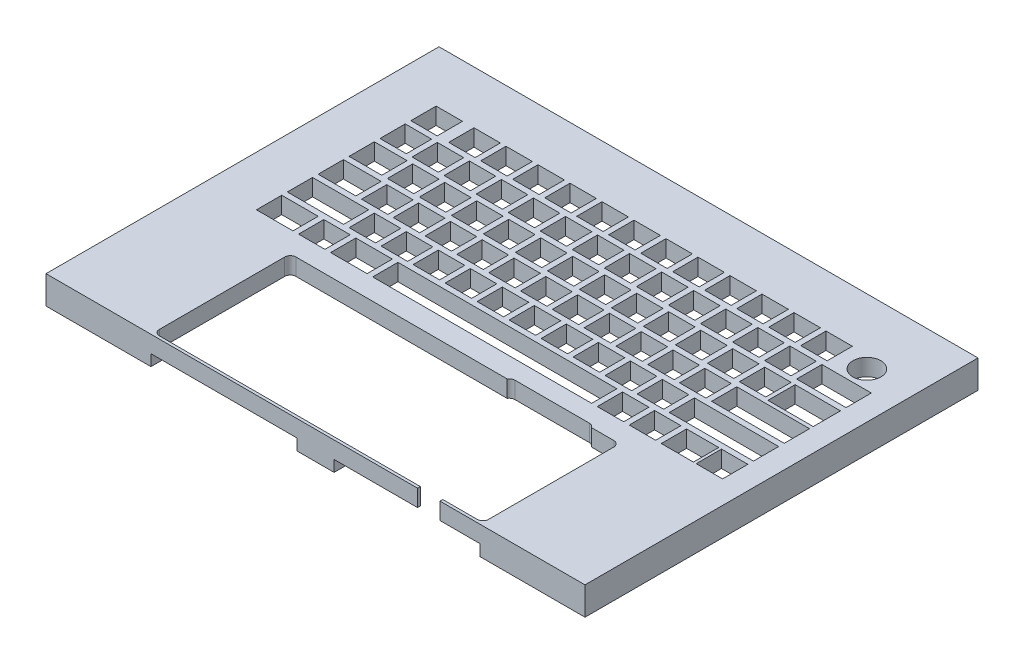
SolidWorks part; units mm, degrees
ref_plane "Front Plane" through (0, 0, 0) normal (0, 0, 1) x (1, 0, 0)
ref_plane "Top Plane" through (0, 0, 0) normal (0, 1, 0) x (1, 0, 0)
ref_plane "Right Plane" through (0, 0, 0) normal (1, 0, 0) x (0, 0, -1)
sketch "Sketch1" plane through (0, 0, 0) normal (0, 1, 0) x (1, 0, 0)
  line L0 (5.08, 5.08) -> (238.76, 5.08)
  line L1 (0, 0) -> (243.84, 0)
  line L2 (0, 0) -> (0, 177.8)
  line L3 (0, 177.8) -> (243.84, 177.8)
  line L4 (243.84, 0) -> (243.84, 177.8)
  line L5 (238.76, 5.08) -> (238.76, 172.72)
  line L6 (5.08, 172.72) -> (238.76, 172.72)
  line L7 (5.08, 5.08) -> (5.08, 172.72)
  dimension "D1" = 177.8
  dimension "D2" = 243.84
  dimension "D3" = 5.08
extrude "Boss-Extrude7" add sketch "Sketch1" along normal blind 12.7
sketch "Sketch6" plane through (0, 12.7, 0) normal (0, 1, 0) x (1, 0, 0)
  line L0 (5.08, 172.72) -> (5.08, 5.08)
  line L1 (5.08, 5.08) -> (238.76, 5.08)
  line L2 (238.76, 5.08) -> (238.76, 172.72)
  line L3 (238.76, 172.72) -> (5.08, 172.72)
extrude "Boss-Extrude8" add sketch "Sketch6" against normal blind 7.62
sketch "Sketch7" plane through (0, 12.7, 0) normal (0, 1, 0) x (1, 0, 0)
  line L0 (0, 0) -> (243.84, 0) construction
  line L1 (0, 177.8) -> (0, 0) construction
  line L2 (243.84, 0) -> (243.84, 177.8) construction
  line L3 (196.37, 1.27) -> (178.2581, 1.27)
  line L4 (47.47, 1.27) -> (47.47, 63.07)
  line L6 (196.37, 63.07) -> (196.37, 1.27)
  line L8 (47.47, 32.17) -> (0, 32.17) construction
  line L9 (196.37, 32.17) -> (243.84, 32.17) construction
  line L11 (168.0981, 0) -> (178.2581, 0)
  line L12 (178.2581, 0) -> (178.2581, 1.27)
  line L14 (157.9954, 1.27) -> (47.47, 1.27)
  line L15 (157.9954, 1.27) -> (168.0981, 1.27)
  line L16 (168.0981, 1.27) -> (168.0981, 0)
  line L18 (183.67, 64.34) -> (145.57, 64.34)
  line L20 (196.37, 63.07) -> (183.67, 63.07)
  line L21 (145.57, 63.07) -> (47.47, 63.07)
  line L22 (183.67, 63.07) -> (183.67, 64.34)
  line L23 (145.57, 63.07) -> (145.57, 64.34)
  dimension "D1" = 1.27
  dimension "D2" = 148.9
  dimension "D3" = 61.8
  dimension "D4" = 10.16
  dimension "D5" = 38.1
  dimension "D6" = 12.7
  dimension "D7" = 1.27
extrude "Cut-Extrude2" cut sketch "Sketch7" against normal blind 8 contours L4 L21 L23 L18 L22 L20 L6 L3 L12 L11 L16 L15 L14
fillet "Fillet1" radius 2.54 4 edges at (47.47, 8.89, -63.07) (47.47, 8.7, -1.27) (196.37, 8.7, -1.27) (196.37, 8.89, -63.07)
fillet "Fillet2" radius 2.54 2 edges at (145.57, 8.89, -64.34) (183.67, 8.89, -64.34)
sketch "Sketch8" plane through (0, 12.7, 0) normal (0, 1, 0) x (1, 0, 0)
  line L0 (50.5293, 86.591) -> (50.5293, 97.9956)
  line L1 (50.5293, 97.9956) -> (62.5181, 97.9956)
  line L2 (62.5181, 97.9956) -> (62.5181, 86.591)
  line L3 (62.5181, 86.591) -> (50.5293, 86.591)
  line L4 (76.9961, 86.591) -> (65.0073, 86.591)
  line L5 (65.0073, 86.591) -> (65.0073, 97.9956)
  line L6 (65.0073, 97.9956) -> (76.9961, 97.9956)
  line L7 (76.9961, 97.9956) -> (76.9961, 86.591)
  line L8 (91.4741, 86.591) -> (79.4853, 86.591)
  line L9 (79.4853, 86.591) -> (79.4853, 97.9956)
  line L10 (79.4853, 97.9956) -> (91.4741, 97.9956)
  line L11 (91.4741, 97.9956) -> (91.4741, 86.591)
  line L12 (105.9521, 86.591) -> (93.9633, 86.591)
  line L13 (93.9633, 86.591) -> (93.9633, 97.9956)
  line L14 (93.9633, 97.9956) -> (105.9521, 97.9956)
  line L15 (105.9521, 97.9956) -> (105.9521, 86.591)
  line L16 (120.4301, 86.591) -> (108.4413, 86.591)
  line L17 (108.4413, 86.591) -> (108.4413, 97.9956)
  line L18 (108.4413, 97.9956) -> (120.4301, 97.9956)
  line L19 (120.4301, 97.9956) -> (120.4301, 86.591)
  line L20 (134.9081, 86.591) -> (122.9193, 86.591)
  line L21 (122.9193, 86.591) -> (122.9193, 97.9956)
  line L22 (122.9193, 97.9956) -> (134.9081, 97.9956)
  line L23 (134.9081, 97.9956) -> (134.9081, 86.591)
  line L24 (149.3861, 86.591) -> (137.3973, 86.591)
  line L25 (137.3973, 86.591) -> (137.3973, 97.9956)
  line L26 (137.3973, 97.9956) -> (149.3861, 97.9956)
  line L27 (149.3861, 97.9956) -> (149.3861, 86.591)
  line L28 (163.8641, 86.591) -> (151.8753, 86.591)
  line L29 (151.8753, 86.591) -> (151.8753, 97.9956)
  line L30 (151.8753, 97.9956) -> (163.8641, 97.9956)
  line L31 (163.8641, 97.9956) -> (163.8641, 86.591)
  line L32 (178.3421, 86.591) -> (166.3533, 86.591)
  line L33 (166.3533, 86.591) -> (166.3533, 97.9956)
  line L34 (166.3533, 97.9956) -> (178.3421, 97.9956)
  line L35 (178.3421, 97.9956) -> (178.3421, 86.591)
  line L36 (192.8201, 86.591) -> (180.8313, 86.591)
  line L37 (180.8313, 86.591) -> (180.8313, 97.9956)
  line L38 (180.8313, 97.9956) -> (192.8201, 97.9956)
  line L39 (192.8201, 97.9956) -> (192.8201, 86.591)
  line L40 (120.4301, 92.2933) -> (122.9193, 92.2933) construction
  line L43 (120.4301, 92.2933) -> (0, 92.2933) construction
  line L44 (0, 177.8) -> (0, 0) construction
  line L45 (47.9893, 86.591) -> (22.5893, 86.591)
  line L46 (22.5893, 86.591) -> (22.5893, 97.9956)
  line L47 (22.5893, 97.9956) -> (47.9893, 97.9956)
  line L48 (47.9893, 97.9956) -> (47.9893, 86.591)
  line L55 (195.3601, 97.9956) -> (195.3601, 86.591)
  line L56 (195.3601, 86.591) -> (233.4601, 86.591)
  line L57 (233.4601, 86.591) -> (233.4601, 97.9956)
  line L58 (233.4601, 97.9956) -> (195.3601, 97.9956)
  line L59 (192.8201, 86.591) -> (195.3601, 86.591) construction
  line L60 (192.8201, 97.9956) -> (195.3601, 97.9956) construction
  line L61 (75.1673, 72.621) -> (75.1673, 84.051)
  line L62 (75.1673, 84.051) -> (174.2273, 84.051)
  line L63 (174.2273, 84.051) -> (174.2273, 72.621)
  line L64 (174.2273, 72.621) -> (75.1673, 72.621)
  line L65 (72.6273, 72.6364) -> (72.6273, 84.051)
  line L66 (72.6273, 84.051) -> (56.1173, 84.051)
  line L67 (56.1173, 84.051) -> (56.1173, 72.6364)
  line L68 (56.1173, 72.6364) -> (72.6273, 72.6364)
  line L69 (53.5773, 72.621) -> (53.5773, 84.051)
  line L70 (53.5773, 84.051) -> (41.6393, 84.051)
  line L71 (41.6393, 84.051) -> (41.6393, 72.621)
  line L72 (41.6393, 72.621) -> (53.5773, 72.621)
  line L73 (39.0993, 72.621) -> (39.0993, 84.051)
  line L74 (39.0993, 84.051) -> (22.5893, 84.051)
  line L75 (22.5893, 84.051) -> (22.5893, 72.621)
  line L76 (22.5893, 72.621) -> (39.0993, 72.621)
  line L78 (188.7052, 72.6364) -> (188.7052, 84.0664)
  line L79 (188.7052, 84.0664) -> (176.7672, 84.0664)
  line L80 (176.7672, 84.0664) -> (176.7672, 72.6364)
  line L81 (176.7672, 72.6364) -> (188.7052, 72.6364)
  line L96 (42.1943, 111.9656) -> (42.1943, 100.5356)
  line L97 (42.1943, 100.5356) -> (54.1323, 100.5356)
  line L98 (54.1323, 100.5356) -> (54.1323, 111.9656)
  line L99 (54.1323, 111.9656) -> (42.1943, 111.9656)
  line L100 (68.5217, 111.9656) -> (56.5837, 111.9656)
  line L101 (56.5837, 111.9656) -> (56.5837, 100.5356)
  line L102 (56.5837, 100.5356) -> (68.5217, 100.5356)
  line L103 (68.5217, 100.5356) -> (68.5217, 111.9656)
  line L104 (82.911, 111.9656) -> (70.973, 111.9656)
  line L105 (70.973, 111.9656) -> (70.973, 100.5356)
  line L106 (70.973, 100.5356) -> (82.911, 100.5356)
  line L107 (82.911, 100.5356) -> (82.911, 111.9656)
  line L108 (97.3003, 111.9656) -> (85.3623, 111.9656)
  line L109 (85.3623, 111.9656) -> (85.3623, 100.5356)
  line L110 (85.3623, 100.5356) -> (97.3003, 100.5356)
  line L111 (97.3003, 100.5356) -> (97.3003, 111.9656)
  line L112 (111.6896, 111.9656) -> (99.7516, 111.9656)
  line L113 (99.7516, 111.9656) -> (99.7516, 100.5356)
  line L114 (99.7516, 100.5356) -> (111.6896, 100.5356)
  line L115 (111.6896, 100.5356) -> (111.6896, 111.9656)
  line L116 (126.079, 111.9656) -> (114.141, 111.9656)
  line L117 (114.141, 111.9656) -> (114.141, 100.5356)
  line L118 (114.141, 100.5356) -> (126.079, 100.5356)
  line L119 (126.079, 100.5356) -> (126.079, 111.9656)
  line L120 (140.4683, 111.9656) -> (128.5303, 111.9656)
  line L121 (128.5303, 111.9656) -> (128.5303, 100.5356)
  line L122 (128.5303, 100.5356) -> (140.4683, 100.5356)
  line L123 (140.4683, 100.5356) -> (140.4683, 111.9656)
  line L124 (154.8576, 111.9656) -> (142.9196, 111.9656)
  line L125 (142.9196, 111.9656) -> (142.9196, 100.5356)
  line L126 (142.9196, 100.5356) -> (154.8576, 100.5356)
  line L127 (154.8576, 100.5356) -> (154.8576, 111.9656)
  line L128 (169.247, 111.9656) -> (157.309, 111.9656)
  line L129 (157.309, 111.9656) -> (157.309, 100.5356)
  line L130 (157.309, 100.5356) -> (169.247, 100.5356)
  line L131 (169.247, 100.5356) -> (169.247, 111.9656)
  line L132 (183.6363, 111.9656) -> (171.6983, 111.9656)
  line L133 (171.6983, 111.9656) -> (171.6983, 100.5356)
  line L134 (171.6983, 100.5356) -> (183.6363, 100.5356)
  line L135 (183.6363, 100.5356) -> (183.6363, 111.9656)
  line L136 (198.0256, 111.9656) -> (186.0876, 111.9656)
  line L137 (186.0876, 111.9656) -> (186.0876, 100.5356)
  line L138 (186.0876, 100.5356) -> (198.0256, 100.5356)
  line L139 (198.0256, 100.5356) -> (198.0256, 111.9656)
  line L140 (39.6543, 100.5356) -> (22.5893, 100.5356)
  line L141 (22.5893, 100.5356) -> (22.5893, 111.9656)
  line L142 (22.5893, 111.9656) -> (39.6543, 111.9656)
  line L143 (39.6543, 111.9656) -> (39.6543, 100.5356)
  line L144 (200.5656, 111.9656) -> (200.5656, 100.5356)
  line L145 (200.5656, 100.5356) -> (233.4601, 100.5356)
  line L146 (233.4601, 100.5356) -> (233.4601, 111.9656)
  line L147 (233.4601, 111.9656) -> (200.5656, 111.9656)
  line L156 (51.8757, 125.9592) -> (39.9377, 125.9592)
  line L157 (39.9377, 125.9592) -> (39.9377, 114.5056)
  line L158 (39.9377, 114.5056) -> (51.8757, 114.5056)
  line L159 (51.8757, 114.5056) -> (51.8757, 125.9592)
  line L196 (66.3537, 125.9592) -> (54.4157, 125.9592)
  line L197 (54.4157, 125.9592) -> (54.4157, 114.5056)
  line L198 (54.4157, 114.5056) -> (66.3537, 114.5056)
  line L199 (66.3537, 114.5056) -> (66.3537, 125.9592)
  line L200 (80.8317, 125.9592) -> (68.8937, 125.9592)
  line L201 (68.8937, 125.9592) -> (68.8937, 114.5056)
  line L202 (68.8937, 114.5056) -> (80.8317, 114.5056)
  line L203 (80.8317, 114.5056) -> (80.8317, 125.9592)
  line L204 (95.3097, 125.9592) -> (83.3717, 125.9592)
  line L205 (83.3717, 125.9592) -> (83.3717, 114.5056)
  line L206 (83.3717, 114.5056) -> (95.3097, 114.5056)
  line L207 (95.3097, 114.5056) -> (95.3097, 125.9592)
  line L208 (109.7877, 125.9592) -> (97.8497, 125.9592)
  line L209 (97.8497, 125.9592) -> (97.8497, 114.5056)
  line L210 (97.8497, 114.5056) -> (109.7877, 114.5056)
  line L211 (109.7877, 114.5056) -> (109.7877, 125.9592)
  line L212 (124.2657, 125.9592) -> (112.3277, 125.9592)
  line L213 (112.3277, 125.9592) -> (112.3277, 114.5056)
  line L214 (112.3277, 114.5056) -> (124.2657, 114.5056)
  line L215 (124.2657, 114.5056) -> (124.2657, 125.9592)
  line L216 (138.7437, 125.9592) -> (126.8057, 125.9592)
  line L217 (126.8057, 125.9592) -> (126.8057, 114.5056)
  line L218 (126.8057, 114.5056) -> (138.7437, 114.5056)
  line L219 (138.7437, 114.5056) -> (138.7437, 125.9592)
  line L220 (153.2217, 125.9592) -> (141.2837, 125.9592)
  line L221 (141.2837, 125.9592) -> (141.2837, 114.5056)
  line L222 (141.2837, 114.5056) -> (153.2217, 114.5056)
  line L223 (153.2217, 114.5056) -> (153.2217, 125.9592)
  line L224 (167.6997, 125.9592) -> (155.7617, 125.9592)
  line L225 (155.7617, 125.9592) -> (155.7617, 114.5056)
  line L226 (155.7617, 114.5056) -> (167.6997, 114.5056)
  line L227 (167.6997, 114.5056) -> (167.6997, 125.9592)
  line L228 (182.1777, 125.9592) -> (170.2397, 125.9592)
  line L229 (170.2397, 125.9592) -> (170.2397, 114.5056)
  line L230 (170.2397, 114.5056) -> (182.1777, 114.5056)
  line L231 (182.1777, 114.5056) -> (182.1777, 125.9592)
  line L232 (196.6557, 125.9592) -> (184.7177, 125.9592)
  line L233 (184.7177, 125.9592) -> (184.7177, 114.5056)
  line L234 (184.7177, 114.5056) -> (196.6557, 114.5056)
  line L235 (196.6557, 114.5056) -> (196.6557, 125.9592)
  line L236 (211.1337, 125.9592) -> (199.1957, 125.9592)
  line L237 (199.1957, 125.9592) -> (199.1957, 114.5056)
  line L238 (199.1957, 114.5056) -> (211.1337, 114.5056)
  line L239 (211.1337, 114.5056) -> (211.1337, 125.9592)
  line L240 (37.3977, 114.5056) -> (22.5893, 114.5056)
  line L241 (22.5893, 114.5056) -> (22.5893, 125.9592)
  line L242 (22.5893, 125.9592) -> (37.3977, 125.9592)
  line L243 (37.3977, 125.9592) -> (37.3977, 114.5056)
  line L244 (212.9454, 113.6508) -> (212.9454, 125.9592)
  line L245 (212.9454, 125.9592) -> (233.4601, 125.9592)
  line L246 (233.4601, 125.9592) -> (233.4601, 113.6508)
  line L247 (233.4601, 113.6508) -> (212.9454, 113.6508)
  line L248 (22.5893, 128.4992) -> (22.5893, 139.9292)
  line L249 (22.5893, 139.9292) -> (34.5273, 139.9292)
  line L250 (34.5273, 139.9292) -> (34.5273, 128.4992)
  line L251 (34.5273, 128.4992) -> (22.5893, 128.4992)
  line L252 (49.0288, 128.4992) -> (37.0908, 128.4992)
  line L253 (37.0908, 128.4992) -> (37.0908, 139.9292)
  line L254 (37.0908, 139.9292) -> (49.0288, 139.9292)
  line L255 (49.0288, 139.9292) -> (49.0288, 128.4992)
  line L256 (63.5303, 128.4992) -> (51.5923, 128.4992)
  line L257 (51.5923, 128.4992) -> (51.5923, 139.9292)
  line L258 (51.5923, 139.9292) -> (63.5303, 139.9292)
  line L259 (63.5303, 139.9292) -> (63.5303, 128.4992)
  line L260 (78.0318, 128.4992) -> (66.0938, 128.4992)
  line L261 (66.0938, 128.4992) -> (66.0938, 139.9292)
  line L262 (66.0938, 139.9292) -> (78.0318, 139.9292)
  line L263 (78.0318, 139.9292) -> (78.0318, 128.4992)
  line L264 (92.5334, 128.4992) -> (80.5954, 128.4992)
  line L265 (80.5954, 128.4992) -> (80.5954, 139.9292)
  line L266 (80.5954, 139.9292) -> (92.5334, 139.9292)
  line L267 (92.5334, 139.9292) -> (92.5334, 128.4992)
  line L268 (107.0349, 128.4992) -> (95.0969, 128.4992)
  line L269 (95.0969, 128.4992) -> (95.0969, 139.9292)
  line L270 (95.0969, 139.9292) -> (107.0349, 139.9292)
  line L271 (107.0349, 139.9292) -> (107.0349, 128.4992)
  line L272 (121.5364, 128.4992) -> (109.5984, 128.4992)
  line L273 (109.5984, 128.4992) -> (109.5984, 139.9292)
  line L274 (109.5984, 139.9292) -> (121.5364, 139.9292)
  line L275 (121.5364, 139.9292) -> (121.5364, 128.4992)
  line L276 (136.0379, 128.4992) -> (124.0999, 128.4992)
  line L277 (124.0999, 128.4992) -> (124.0999, 139.9292)
  line L278 (124.0999, 139.9292) -> (136.0379, 139.9292)
  line L279 (136.0379, 139.9292) -> (136.0379, 128.4992)
  line L280 (150.5395, 128.4992) -> (138.6015, 128.4992)
  line L281 (138.6015, 128.4992) -> (138.6015, 139.9292)
  line L282 (138.6015, 139.9292) -> (150.5395, 139.9292)
  line L283 (150.5395, 139.9292) -> (150.5395, 128.4992)
  line L284 (165.041, 128.4992) -> (153.103, 128.4992)
  line L285 (153.103, 128.4992) -> (153.103, 139.9292)
  line L286 (153.103, 139.9292) -> (165.041, 139.9292)
  line L287 (165.041, 139.9292) -> (165.041, 128.4992)
  line L288 (179.5425, 128.4992) -> (167.6045, 128.4992)
  line L289 (167.6045, 128.4992) -> (167.6045, 139.9292)
  line L290 (167.6045, 139.9292) -> (179.5425, 139.9292)
  line L291 (179.5425, 139.9292) -> (179.5425, 128.4992)
  line L292 (194.044, 128.4992) -> (182.106, 128.4992)
  line L293 (182.106, 128.4992) -> (182.106, 139.9292)
  line L294 (182.106, 139.9292) -> (194.044, 139.9292)
  line L295 (194.044, 139.9292) -> (194.044, 128.4992)
  line L296 (208.5455, 128.4992) -> (196.6075, 128.4992)
  line L297 (196.6075, 128.4992) -> (196.6075, 139.9292)
  line L298 (196.6075, 139.9292) -> (208.5455, 139.9292)
  line L299 (208.5455, 139.9292) -> (208.5455, 128.4992)
  line L300 (211.0855, 128.4992) -> (233.4601, 128.4992)
  line L301 (233.4601, 128.4992) -> (233.4601, 139.9292)
  line L302 (233.4601, 139.9292) -> (211.0855, 139.9292)
  line L303 (211.0855, 139.9292) -> (211.0855, 128.4992)
  line L304 (221.5221, 72.621) -> (221.5221, 84.0664)
  line L305 (221.5221, 84.0664) -> (233.4601, 84.0664)
  line L306 (233.4601, 84.0664) -> (233.4601, 72.621)
  line L307 (233.4601, 72.621) -> (221.5221, 72.621)
  line L308 (191.2452, 72.621) -> (191.2452, 84.0664)
  line L309 (191.2452, 84.0664) -> (203.1832, 84.0664)
  line L310 (203.1832, 84.0664) -> (203.1832, 72.621)
  line L311 (203.1832, 72.621) -> (191.2452, 72.621)
  line L318 (205.7232, 84.0664) -> (205.7232, 72.621)
  line L319 (205.7232, 72.621) -> (220.2767, 72.621)
  line L320 (220.2767, 72.621) -> (220.2767, 84.0664)
  line L321 (220.2767, 84.0664) -> (205.7232, 84.0664)
  line L322 (22.5893, 142.4692) -> (22.5893, 153.8992)
  line L323 (22.5893, 153.8992) -> (34.5273, 153.8992)
  line L324 (34.5273, 153.8992) -> (34.5273, 142.4692)
  line L325 (34.5273, 142.4692) -> (22.5893, 142.4692)
  line L326 (39.6543, 142.5358) -> (39.6543, 153.9658)
  line L327 (39.6543, 153.9658) -> (51.5923, 153.9658)
  line L328 (51.5923, 153.9658) -> (51.5923, 142.5358)
  line L329 (51.5923, 142.5358) -> (39.6543, 142.5358)
  line L330 (66.0703, 142.5358) -> (54.1323, 142.5358)
  line L331 (54.1323, 142.5358) -> (54.1323, 153.9658)
  line L332 (54.1323, 153.9658) -> (66.0703, 153.9658)
  line L333 (66.0703, 153.9658) -> (66.0703, 142.5358)
  line L334 (80.5483, 142.5358) -> (68.6103, 142.5358)
  line L335 (68.6103, 142.5358) -> (68.6103, 153.9658)
  line L336 (68.6103, 153.9658) -> (80.5483, 153.9658)
  line L337 (80.5483, 153.9658) -> (80.5483, 142.5358)
  line L338 (95.0263, 142.5358) -> (83.0883, 142.5358)
  line L339 (83.0883, 142.5358) -> (83.0883, 153.9658)
  line L340 (83.0883, 153.9658) -> (95.0263, 153.9658)
  line L341 (95.0263, 153.9658) -> (95.0263, 142.5358)
  line L342 (109.5043, 142.5358) -> (97.5663, 142.5358)
  line L343 (97.5663, 142.5358) -> (97.5663, 153.9658)
  line L344 (97.5663, 153.9658) -> (109.5043, 153.9658)
  line L345 (109.5043, 153.9658) -> (109.5043, 142.5358)
  line L346 (123.9823, 142.5358) -> (112.0443, 142.5358)
  line L347 (112.0443, 142.5358) -> (112.0443, 153.9658)
  line L348 (112.0443, 153.9658) -> (123.9823, 153.9658)
  line L349 (123.9823, 153.9658) -> (123.9823, 142.5358)
  line L350 (138.4603, 142.5358) -> (126.5223, 142.5358)
  line L351 (126.5223, 142.5358) -> (126.5223, 153.9658)
  line L352 (126.5223, 153.9658) -> (138.4603, 153.9658)
  line L353 (138.4603, 153.9658) -> (138.4603, 142.5358)
  line L354 (152.9383, 142.5358) -> (141.0003, 142.5358)
  line L355 (141.0003, 142.5358) -> (141.0003, 153.9658)
  line L356 (141.0003, 153.9658) -> (152.9383, 153.9658)
  line L357 (152.9383, 153.9658) -> (152.9383, 142.5358)
  line L358 (167.4163, 142.5358) -> (155.4783, 142.5358)
  line L359 (155.4783, 142.5358) -> (155.4783, 153.9658)
  line L360 (155.4783, 153.9658) -> (167.4163, 153.9658)
  line L361 (167.4163, 153.9658) -> (167.4163, 142.5358)
  line L362 (181.8943, 142.5358) -> (169.9563, 142.5358)
  line L363 (169.9563, 142.5358) -> (169.9563, 153.9658)
  line L364 (169.9563, 153.9658) -> (181.8943, 153.9658)
  line L365 (181.8943, 153.9658) -> (181.8943, 142.5358)
  line L366 (196.3723, 142.5358) -> (184.4343, 142.5358)
  line L367 (184.4343, 142.5358) -> (184.4343, 153.9658)
  line L368 (184.4343, 153.9658) -> (196.3723, 153.9658)
  line L369 (196.3723, 153.9658) -> (196.3723, 142.5358)
  line L370 (210.8503, 142.5358) -> (198.9123, 142.5358)
  line L371 (198.9123, 142.5358) -> (198.9123, 153.9658)
  line L372 (198.9123, 153.9658) -> (210.8503, 153.9658)
  line L373 (210.8503, 153.9658) -> (210.8503, 142.5358)
  line L374 (51.5923, 142.5358) -> (66.0703, 142.5358) construction
  circle A0 centre (222.9667, 148.4094) radius 6.35
  dimension "D1" = 11.9888
  dimension "D2" = 11.4046
  dimension "D4" = 25.4
  dimension "D5" = 2.4892
  dimension "D6" = 2.54
  dimension "D7" = 38.1
  dimension "D8" = 2.54
  dimension "D9" = 99.06
  dimension "D10" = 11.43
  dimension "D11" = 11.43
  dimension "D12" = 2.54
  dimension "D13" = 16.51
  dimension "D14" = 11.938
  dimension "D15" = 16.51
  dimension "D16" = 2.54
  dimension "D17" = 2.54
  dimension "D18" = 2.54
  dimension "D19" = 11.938
  dimension "D20" = 11.4454
  dimension "D21" = 11.43
  dimension "D22" = 2.54
  dimension "D23" = 11.938
  dimension "D24" = 11.938
  dimension "D25" = 2.54
  dimension "D26" = 11.43
  dimension "D27" = 1.2454
  dimension "D28" = 11.938
  dimension "D29" = 11.43
  dimension "D30" = 2.54
  dimension "D32" = 2.54
  dimension "D33" = 2.54
  dimension "D34" = 2.54
  dimension "D35" = 12
  dimension "D36" = 2.54
  dimension "D37" = 2.54
  dimension "D38" = 11.938
  dimension "D39" = 11.43
  dimension "D41" = 2.54
  dimension "D42" = 2.54
  dimension "D43" = 11.938
  dimension "D44" = 2.54
  dimension "D45" = 11.43
  dimension "D46" = 12
  dimension "D47" = 14.478
  dimension "D48" = 2.5635
  dimension "D3" = 10
  dimension "D31" = 11
  dimension "D40" = 13
extrude "Cut-Extrude3" cut sketch "Sketch8" against normal up to next (7.62 mm away) contours L302 L303 L300 L301 | L247 L246 L245 L244 | L146 L147 L144 L145 | L57 L58 L55 L56 | L307 L306 L305 L304 | L320 L321 L318 L319 | L311 L310 L309 L308 | L80 L81 L78 L79 | L39 L38 L37 L36 | L134 L135 L132 L133 | L138 L139 L136 L137 | L234 L235 L232 L233 | L238 L239 L236 L237 | L373 L372 L371 L370 | L369 L368 L367 L366 | L295 L294 L293 L292 | L365 L364 L363 L362 | L291 L290 L289 L288 | L230 L231 L228 L229 | L64 L63 L62 L61 | L75 L76 L73 L74 | L71 L72 L69 L70 | L67 L68 L65 L66 | L48 L47 L46 L45 | L143 L142 L141 L140 | L98 L99 L96 L97 | L102 L103 L100 L101 | L106 L107 L104 L105 | L110 L111 L108 L109 | L11 L10 L9 L8 | L3 L2 L1 L0 | L7 L6 L5 L4 | L114 L115 L112 L113 | L15 L14 L13 L12 | L19 L18 L17 L16 | L23 L22 L21 L20 | L118 L119 L116 L117 | L122 L123 L120 L121 | L27 L26 L25 L24 | L31 L30 L29 L28 | L126 L127 L124 L125 | L130 L131 L128 L129 | L226 L227 L224 L225 | L222 L223 L220 L221 | L218 L219 L216 L217 | L214 L215 L212 L213 | L210 L211 L208 L209 | L206 L207 L204 L205 | L202 L203 L200 L201 | L198 L199 L196 L197 | L158 L159 L156 L157 | L243 L242 L241 L240 | L251 L250 L249 L248 | L325 L324 L323 L322 | L329 L328 L327 L326 | L255 L254 L253 L252 | L259 L258 L257 L256 | L333 L332 L331 L330 | L337 L336 L335 L334 | L263 L262 L261 L260 | L267 L266 L265 L264 | L341 L340 L339 L338 | L345 L344 L343 L342 | L271 L270 L269 L268 | L275 L274 L273 L272 | L349 L348 L347 L346 | L353 L352 L351 L350 | L279 L278 L277 L276 | L283 L282 L281 L280 | L357 L356 L355 L354 | L361 L360 L359 L358 | L287 L286 L285 L284 | A0 | L34 L35 L32 L33 | L298 L299 L296 L297 region at (56.5237, 12.7, -92.2933) region at (71.0017, 12.7, -92.2933) region at (85.4797, 12.7, -92.2933) region at (99.9577, 12.7, -92.2933) region at (114.4357, 12.7, -92.2933) region at (128.9137, 12.7, -92.2933) region at (143.3917, 12.7, -92.2933) region at (157.8697, 12.7, -92.2933) region at (186.8257, 12.7, -92.2933) region at (35.2893, 12.7, -92.2933) region at (214.4101, 12.7, -92.2933) region at (124.6973, 12.7, -78.336) region at (64.3723, 12.7, -78.3437) region at (47.6083, 12.7, -78.336) region at (30.8443, 12.7, -78.336) region at (182.7362, 12.7, -78.3514) region at (48.1633, 12.7, -106.2506) region at (62.5527, 12.7, -106.2506) region at (76.942, 12.7, -106.2506) region at (91.3313, 12.7, -106.2506) region at (105.7206, 12.7, -106.2506) region at (120.11, 12.7, -106.2506) region at (134.4993, 12.7, -106.2506) region at (148.8886, 12.7, -106.2506) region at (163.278, 12.7, -106.2506) region at (177.6673, 12.7, -106.2506) region at (192.0566, 12.7, -106.2506) region at (31.1218, 12.7, -106.2506) region at (217.0128, 12.7, -106.2506) region at (45.9067, 12.7, -120.2324) region at (60.3847, 12.7, -120.2324) region at (74.8627, 12.7, -120.2324) region at (89.3407, 12.7, -120.2324) region at (103.8187, 12.7, -120.2324) region at (118.2967, 12.7, -120.2324) region at (132.7747, 12.7, -120.2324) region at (147.2527, 12.7, -120.2324) region at (161.7307, 12.7, -120.2324) region at (176.2087, 12.7, -120.2324) region at (190.6867, 12.7, -120.2324) region at (205.1647, 12.7, -120.2324) region at (29.9935, 12.7, -120.2324) region at (223.2027, 12.7, -119.805) region at (28.5583, 12.7, -134.2142) region at (43.0598, 12.7, -134.2142) region at (57.5613, 12.7, -134.2142) region at (72.0628, 12.7, -134.2142) region at (86.5644, 12.7, -134.2142) region at (101.0659, 12.7, -134.2142) region at (115.5674, 12.7, -134.2142) region at (130.0689, 12.7, -134.2142) region at (144.5705, 12.7, -134.2142) region at (159.072, 12.7, -134.2142) region at (173.5735, 12.7, -134.2142) region at (188.075, 12.7, -134.2142) region at (222.2728, 12.7, -134.2142) region at (227.4911, 12.7, -78.3437) region at (197.2142, 12.7, -78.3437) region at (213, 12.7, -78.3437) region at (28.5583, 12.7, -148.1842)
sketch "Sketch10" plane through (0, 5.08, 0) normal (0, -1, 0) x (1, 0, 0)
  line L0 (50.01, -63.07) -> (47.47, -63.07) construction
  line L1 (47.47, -63.07) -> (47.47, -60.53) construction
  arc A0 (47.47, -60.53) -> (50.01, -63.07) centre (50.01, -60.53) ccw construction
  circle A1 centre (47.47, -63.07) radius 0.7937
  dimension "D1" = 1.5875
sketch "Sketch12" plane through (0, 0, -5.08) normal (0, 0, -1) x (-1, 0, 0)
  line L0 (-47.47, 4.7) -> (-47.47, 0) construction
  line L1 (-5.08, 0) -> (-238.76, 0) construction
sketch "Sketch19" plane through (0, 0, 0) normal (0, -1, 0) x (1, 0, 0)
  line L0 (0, 0) -> (243.84, 0) construction
  line L1 (47.47, -5.08) -> (113.51, -5.08)
  line L2 (47.47, -5.08) -> (47.47, 0)
  line L3 (47.47, 0) -> (113.51, 0)
  line L4 (113.51, -5.08) -> (113.51, 0)
  dimension "D1" = 66.04
sketch "Sketch20" plane through (0, 0, -5.08) normal (0, 0, -1) x (-1, 0, 0)
  line L0 (-196.37, 5.08) -> (-196.37, 0)
  line L1 (-5.08, 0) -> (-238.76, 0) construction
sketch "Sketch21" plane through (0, 0, 0) normal (0, -1, 0) x (1, 0, 0)
  line L0 (0, 0) -> (243.84, 0) construction
  line L1 (196.37, -5.08) -> (130.33, -5.08)
  line L2 (196.37, -5.08) -> (196.37, 0)
  line L3 (196.37, 0) -> (130.33, 0)
  line L4 (130.33, -5.08) -> (130.33, 0)
  point P7 (0, 0)
  point P8 (0, 0)
  dimension "D1" = 66.04
extrude "Cut-Extrude5" cut sketch "Sketch19" against normal blind 5.08 contours L4 L3 L2 L1
extrude "Cut-Extrude6" cut sketch "Sketch21" against normal blind 5.08 contours L2 L3 L4 L1
